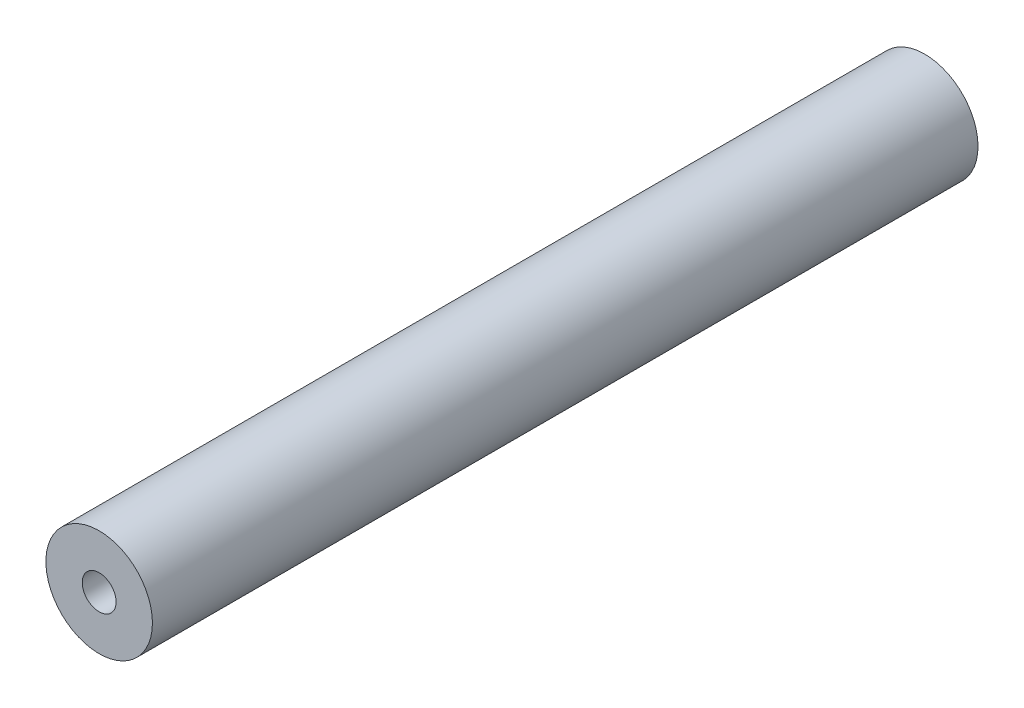
SolidWorks part; units mm, degrees
ref_plane "Front Plane" through (0, 0, 0) normal (0, 0, 1) x (1, 0, 0)
ref_plane "Top Plane" through (0, 0, 0) normal (0, 1, 0) x (1, 0, 0)
ref_plane "Right Plane" through (0, 0, 0) normal (1, 0, 0) x (0, 0, -1)
sketch "Sketch1" plane through (0, 0, 0) normal (0, 0, 1) x (1, 0, 0)
  circle A1 centre (0, 0) radius 6.35
  dimension "D2" = 12.7
extrude "Boss-Extrude1" add sketch "Sketch1" along normal mid plane 98.425 contours A1 region at (0, 0, 0)
hole_wizard "#10-32 Tapped Hole1" positions "3DSketch1" profile "Sketch2" tap size "#10-32" standard "ANSI Inch"
sketch3d "3DSketch1"
  line L0 (0, 0, 49.2125) -> (0, 0, -49.2125) construction
  point P0 (0, 0, -49.2125)
  point P4 (0, 0, 49.2125)
sketch "Sketch2" plane through (0, 0, -49.2125) normal (1, 0, 0) x (0, 1, 0)
  line L0 (0, 0) -> (0, 13.2428)
  line L1 (0, 13.2428) -> (2.0193, 12.0294)
  line L2 (2.0193, 12.0294) -> (2.0193, 0)
  line L5 (2.0193, 0) -> (0, 0)
  line L10 (0, 13.2428) -> (-2.0193, 12.0294) construction
  line L11 (0, -6.35) -> (0, 107.95) construction
  dimension "Tap Drill Dia." = 4.0386
  dimension "Tap Drill Depth" = 12.0294
  dimension "Drill Angle" = 118
cosmetic thread "Hole Thread1"
cosmetic thread "Hole Thread2"
